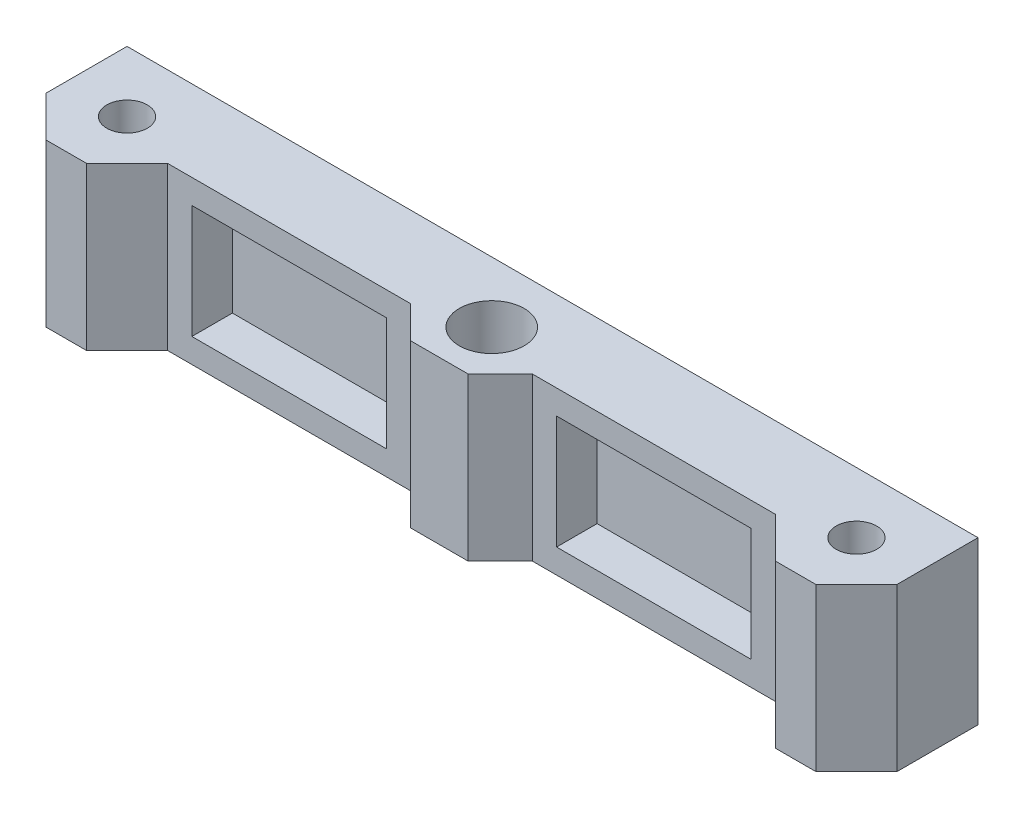
SolidWorks part; units mm, degrees
ref_plane "Front Plane" through (0, 0, 0) normal (0, 0, 1) x (1, 0, 0)
ref_plane "Top Plane" through (0, 0, 0) normal (0, 1, 0) x (1, 0, 0)
ref_plane "Right Plane" through (0, 0, 0) normal (1, 0, 0) x (0, 0, -1)
sketch "Sketch2" plane through (0, 0, 0) normal (0, 1, 0) x (1, 0, 0)
  line L0 (-52.5, -2.5) -> (-52.5, 7.5)
  line L1 (-47.5, -7.5) -> (-42.5, -7.5)
  line L2 (-52.5, 7.5) -> (52.5, 7.5)
  line L3 (52.5, -2.5) -> (52.5, 7.5)
  line L4 (-52.5, -2.5) -> (-47.5, -7.5)
  line L5 (47.5, -7.5) -> (52.5, -2.5)
  line L9 (42.5, -7.5) -> (47.5, -7.5)
  line L14 (-37.5, -2.5) -> (-7.5, -2.5)
  line L18 (7.5, -2.5) -> (37.5, -2.5)
  line L21 (-37.5, -2.5) -> (-42.5, -7.5)
  line L22 (37.5, -2.5) -> (42.5, -7.5)
  line L23 (-7.5, -2.5) -> (-3.5355, -6.4645)
  line L24 (3.5355, -6.4645) -> (7.5, -2.5)
  line L26 (-3.5355, -6.4645) -> (3.5355, -6.4645)
  circle A0 centre (0, 0) radius 4
  circle A1 centre (-45, 0) radius 2.5
  circle A2 centre (45, 0) radius 2.5
  point P5 (-52.5, -7.5)
  point P8 (52.5, -7.5)
  point P21 (0, 0)
  point P23 (0, -10)
  point P24 (0, 0)
  dimension "D1" = 8
  dimension "D2" = 5
  dimension "D3" = 5
  dimension "D4" = 45
  dimension "D5" = 45
  dimension "D6" = 7.5
  dimension "D7" = 7.5
  dimension "D8" = 7.5
  dimension "D9" = 10
  dimension "D10" = 7.5
  dimension "D11" = 7.5
  dimension "D12" = 0
  dimension "D13" = 5
  dimension "D14" = 5
  dimension "D16" = 7.5
  dimension "D17" = 10
  dimension "D18" = 7.5
  dimension "D19" = 2.5
  dimension "D20" = 2.5
extrude "Boss-Extrude1" add sketch "Sketch2" along normal blind 20
sketch "Sketch3" plane through (0, 0, 2.5) normal (0, 0, 1) x (1, 0, 0)
  line L0 (-37.5, 20) -> (-7.5, 20) construction
  line L1 (-34.5, 3) -> (-10.5, 3)
  line L2 (-34.5, 3) -> (-34.5, 17)
  line L3 (-34.5, 17) -> (-10.5, 17)
  line L4 (-10.5, 3) -> (-10.5, 17)
  line L5 (-34.5, 3) -> (-10.5, 17) construction
  line L6 (-34.5, 17) -> (-10.5, 3) construction
  line L7 (10.5, 3) -> (34.5, 3)
  line L8 (10.5, 3) -> (10.5, 17)
  line L9 (10.5, 17) -> (34.5, 17)
  line L10 (34.5, 3) -> (34.5, 17)
  line L11 (10.5, 3) -> (34.5, 17) construction
  line L12 (10.5, 17) -> (34.5, 3) construction
  line L13 (-37.5, 0) -> (-7.5, 0) construction
  line L14 (7.5, 0) -> (37.5, 0) construction
  line L15 (7.5, 20) -> (37.5, 20) construction
  line L16 (-37.5, 20) -> (-37.5, 0) construction
  line L17 (-7.5, 20) -> (-7.5, 0) construction
  line L18 (7.5, 20) -> (7.5, 0) construction
  line L19 (37.5, 20) -> (37.5, 0) construction
  point P0 (-22.5, 10)
  point P5 (22.5, 10)
  point P26 (0, 0)
  point P27 (0, 0)
  dimension "D1" = 3
  dimension "D2" = 3
  dimension "D3" = 3
  dimension "D4" = 3
  dimension "D5" = 3
  dimension "D6" = 3
  dimension "D7" = 3
  dimension "D8" = 3
extrude "Cut-Extrude3" cut sketch "Sketch3" against normal blind 5 contours L8 L7 L10 L9 | L2 L1 L4 L3
